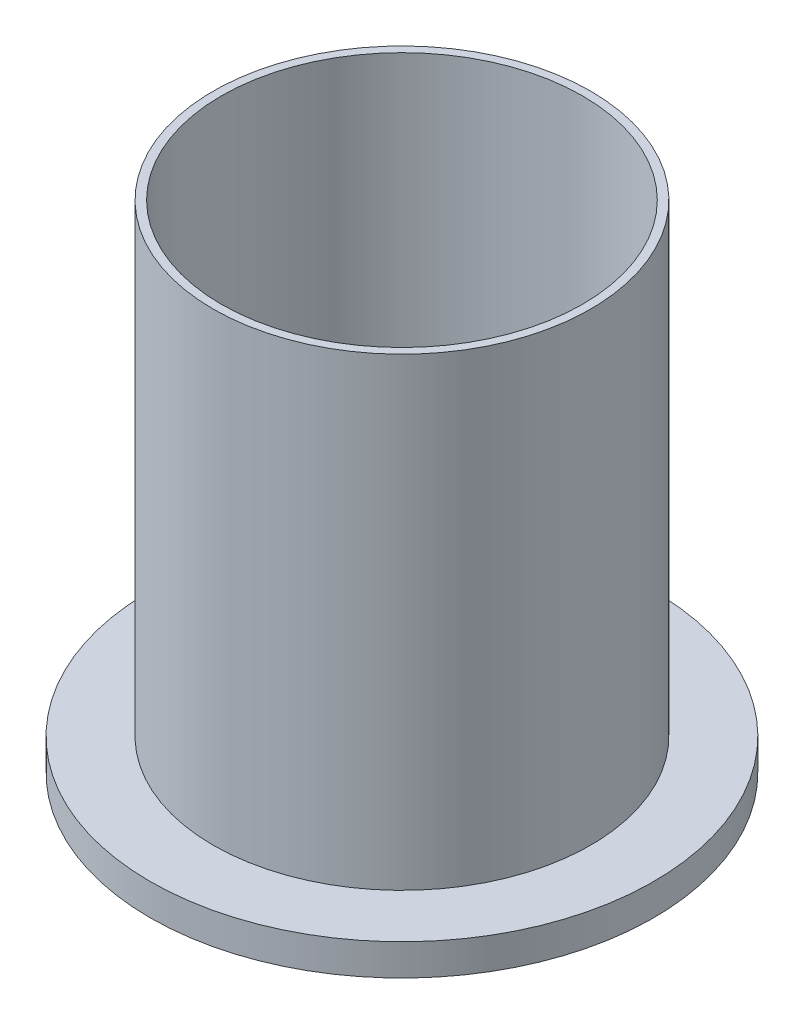
SolidWorks part; units mm, degrees
material "AISI 304"
ref_plane "Front Plane" through (0, 0, 0) normal (0, 0, 1) x (1, 0, 0)
ref_plane "Top Plane" through (0, 0, 0) normal (0, 1, 0) x (1, 0, 0)
ref_plane "Right Plane" through (0, 0, 0) normal (1, 0, 0) x (0, 0, -1)
sketch "Sketch1" plane through (0, 0, 0) normal (0, 1, 0) x (1, 0, 0)
  circle A0 centre (0, 0) radius 36.449
  circle A1 centre (0, 0) radius 38.1
  circle A2 centre (0, 0) radius 50.8
  dimension "D1" = 76.2
  dimension "D2" = 72.898
  dimension "D3" = 101.6
extrude "Boss-Extrude1" add sketch "Sketch1" along normal blind 100.076 contours A1 A0 region at (-37.0224, 0, 0)
extrude "Boss-Extrude2" add sketch "Sketch1<3>" along normal blind 6.35 contours A2 A1 region at (-49.3632, 0, 0)
sketch "Sketch1<3>" plane through (0, 0, 0) normal (0, 1, 0) x (1, 0, 0) same geometry as "Sketch1"
